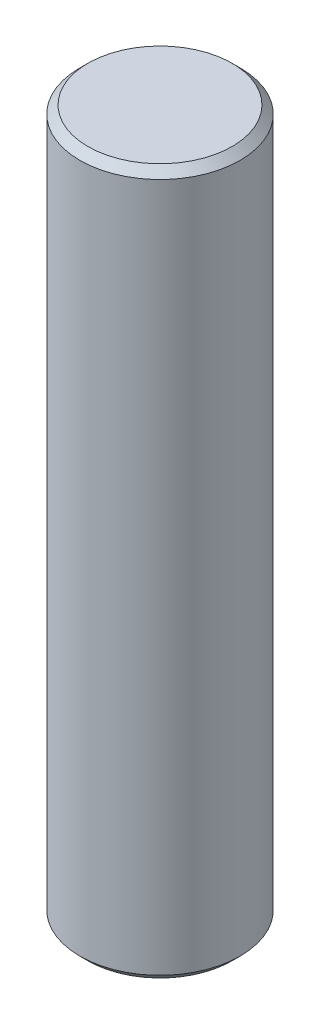
SolidWorks part; units mm, degrees
ref_plane "Front Plane" through (0, 0, 0) normal (0, 0, 1) x (1, 0, 0)
ref_plane "Top Plane" through (0, 0, 0) normal (0, 1, 0) x (1, 0, 0)
ref_plane "Right Plane" through (0, 0, 0) normal (1, 0, 0) x (0, 0, -1)
sketch "Sketch1" plane through (0, 0, 0) normal (0, 1, 0) x (1, 0, 0)
  circle A0 centre (0, 0) radius 2.5
  dimension "D1" = 5
extrude "Boss-Extrude1" add sketch "Sketch1" along normal blind 22
chamfer "Chamfer1" distance 0.25 angle 45 2 edges at (0, 0, 2.5) (0, 22, 2.5)
